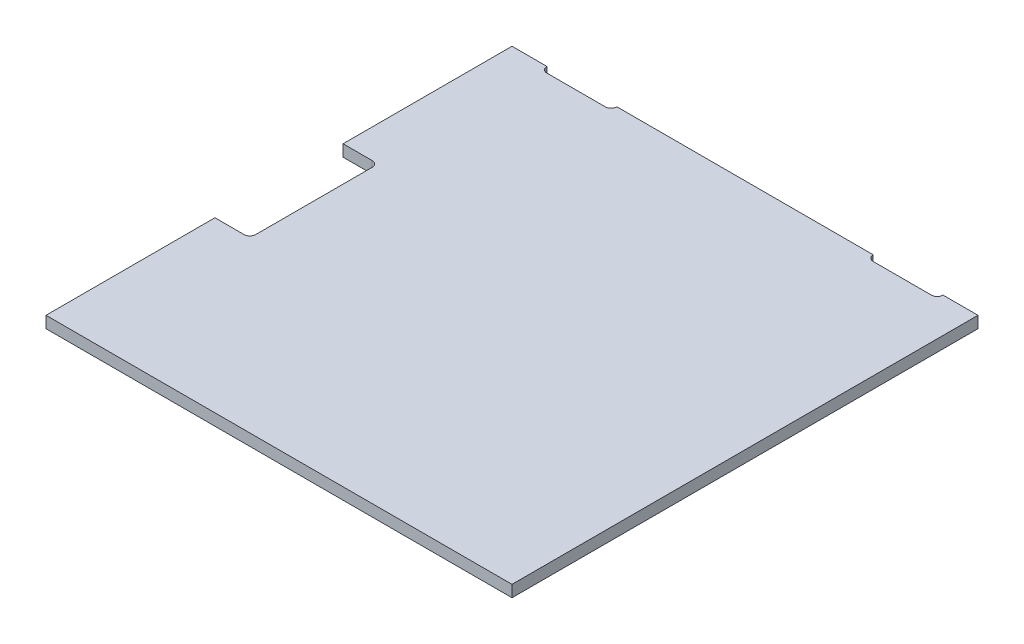
SolidWorks part; units mm, degrees
ref_plane "Front" through (0, 0, 0) normal (0, 0, 1) x (1, 0, 0)
ref_plane "Top" through (0, 0, 0) normal (0, 1, 0) x (1, 0, 0)
ref_plane "Right" through (0, 0, 0) normal (1, 0, 0) x (0, 0, -1)
sketch "草图1" plane through (0, 0, 0) normal (0, 1, 0) x (1, 0, 0)
  line L0 (-40, 11) -> (-40, 40)
  line L1 (-40, -40) -> (40, -40)
  line L2 (-40, -40) -> (-40, -11)
  line L3 (-40, 40) -> (40, 40)
  line L4 (40, -40) -> (40, 40)
  line L5 (-40, -40) -> (40, 40) construction
  line L6 (-40, 40) -> (40, -40) construction
  line L7 (-34, 11) -> (-34, -11)
  line L8 (-34, -11) -> (-40, -11)
  line L9 (-34, 11) -> (-40, 11)
  point P0 (0, 0)
extrude "凸台-拉伸1" add sketch "草图1" along normal blind 2
sketch "草图2" plane through (0, 2, 0) normal (0, 1, 0) x (1, 0, 0)
  line L0 (0, 0) -> (0, 20) construction
  line L1 (40, 40) -> (-40, 40) construction
  line L2 (-34, 40) -> (-34, 39)
  line L3 (-34, 39) -> (-22, 39)
  line L4 (-22, 39) -> (-22, 40)
  line L5 (-22, 40) -> (-34, 40)
  line L6 (22, 40) -> (34, 40)
  line L7 (22, 39) -> (22, 40)
  line L8 (34, 39) -> (22, 39)
  line L9 (34, 40) -> (34, 39)
extrude "切除-拉伸1" cut sketch "草图2" against normal blind 2
fillet "圆角1" radius 1 4 edges at (22, 1, -39) (34, 1, -39) (-34, 1, -39) (-22, 1, -39)
fillet "圆角2" radius 1 2 edges at (-34, 1, 11) (-34, 1, -11)
